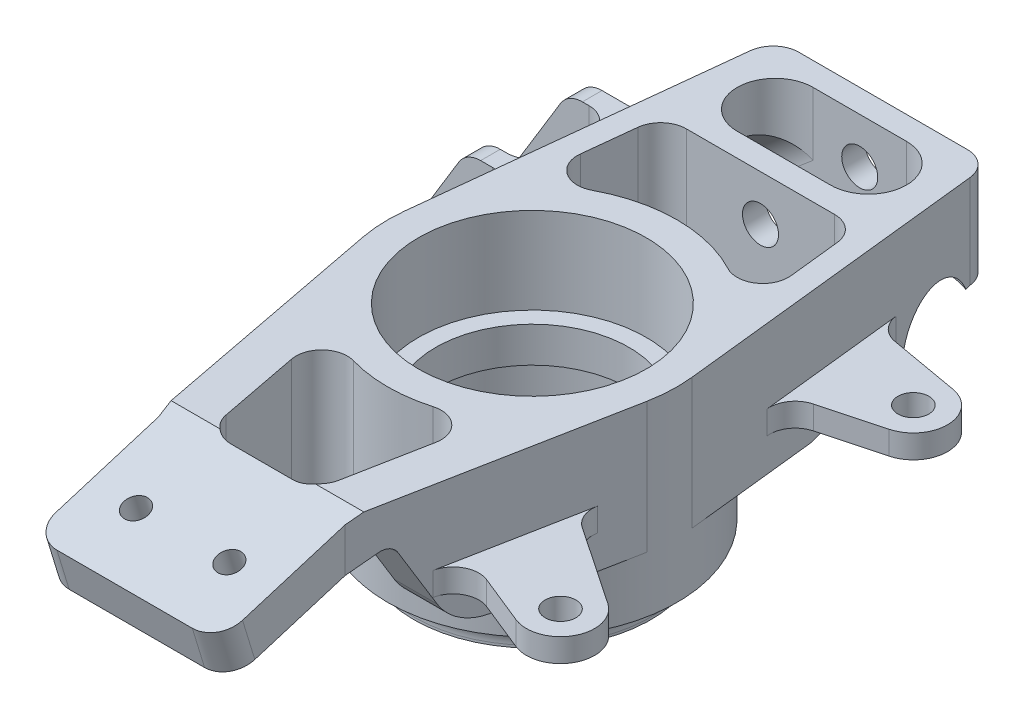
SolidWorks part; units mm, degrees
material "6061-T6 (SS)"
ref_plane "Front Plane" through (0, 0, 0) normal (0, 0, 1) x (1, 0, 0)
ref_plane "Top Plane" through (0, 0, 0) normal (0, 1, 0) x (1, 0, 0)
ref_plane "Right Plane" through (0, 0, 0) normal (1, 0, 0) x (0, 0, -1)
sketch "UBJ LBJ Geometry" plane through (0, 0, 0) normal (1, 0, 0) x (0, 0, -1)
  line L0 (0, 0) -> (0, -97.4059) construction
  line L1 (0, 0) -> (-30.7529, 0) construction
  line L2 (0, 22) -> (-45.5659, 22) construction
  line L3 (0, -10.5425) -> (-23.1063, -10.5425) construction
  line L4 (-84.7344, -51.66) -> (78.74, -22.958) construction
  line L5 (49.4563, 0) -> (49.4563, -88.2735) construction
  circle A0 centre (-84.7344, -51.66) radius 10.3251 construction
  circle A1 centre (78.74, -22.958) radius 10.3251 construction
  dimension "D7" = 20.6502
  dimension "D8" = 20.6502
  dimension "D1" = 22
  dimension "D2" = 32.5425
  dimension "D3" = 44.958
  dimension "D4" = 73.66
  dimension "D5" = 84.7344
  dimension "D6" = 78.74
  dimension "D9" = 29.2837
ref_plane "Wheel Face " through (0, 22, 0) normal (0, -1, 0) x (-1, 0, 0)
ref_plane "Upright Face" through (0, -10.5425, 0) normal (0, -1, 0) x (-1, 0, 0)
ref_plane "Tie Bracket Plane" through (0, 0, -49.4563) normal (0, 0, 1) x (1, 0, 0)
sketch "Tie Bracket Geometry" plane through (0, 0, -49.4563) normal (0, 0, 1) x (1, 0, 0)
  line L0 (0, -28.0995) -> (-60.5599, -51.7108) construction
  line L4 (0, 200000) -> (0, -200097.4059) construction
  circle A0 centre (-60.5599, -51.7108) radius 8.948 construction
  dimension "D1" = 65
  dimension "D2" = 68.7
sketch "Sketch1" plane through (0, 0, 0) normal (0, 0, 1) x (1, 0, 0)
  line L1 (-75.0953, -10.5425) -> (75.0953, -10.5425) construction
  line L2 (-39.37, -10.5425) -> (-39.37, -61.3425)
  line L3 (-39.37, -61.3425) -> (-32.258, -61.3425)
  line L4 (-32.258, -61.3425) -> (-32.258, -68.9625)
  line L5 (-32.258, -68.9625) -> (-30.9829, -68.9625)
  line L8 (-30.9829, -10.5425) -> (-30.9829, -34.0375)
  line L9 (-30.9829, -34.0375) -> (-26.289, -34.0375)
  line L10 (-26.289, -34.0375) -> (-26.289, -43.6895)
  line L11 (-26.289, -43.6895) -> (-30.9829, -43.6895)
  line L12 (-30.9829, -43.6895) -> (-30.9829, -68.9625)
  line L15 (-39.37, -10.5425) -> (-30.9829, -10.5425)
  line L17 (0, 0) -> (0, -23.5057) construction
  dimension "D1" = 9.652
  dimension "D2" = 61.9658
  dimension "D3" = 25.273
  dimension "D4" = 52.578
  dimension "D5" = 23.495
  dimension "D6" = 50.8
  dimension "D7" = 78.74
  dimension "D8" = 64.516
revolve "Bearing Housing Revolve" add sketch "Sketch1" angle 360 about L17
fillet "Bearing Housing Fillet" radius 6.985 1 edges at (0, -61.3425, 32.258)
sketch "Sketch2" plane through (0, -10.5425, 0) normal (0, -1, 0) x (-1, 0, 0)
  line L3 (39.37, -43.18) -> (39.37, 0)
  line L4 (-39.37, -43.18) -> (-39.37, 0)
  line L5 (39.37, -43.18) -> (-39.37, -43.18)
  circle A4 centre (0, 0) radius 39.37 construction
  arc A5 (39.37, 0) -> (-39.37, 0) centre (0, 0) cw
  dimension "D1" = 43.18
extrude "UBJ Prep" add sketch "Sketch2" along normal blind 35.56
sketch "Sketch3" plane through (-39.37, 0, 0) normal (-1, 0, 0) x (0, 0, 1)
  line L0 (-120.7672, 22) -> (120.7672, 22) construction
  line L1 (43.18, -10.5425) -> (72.0727, -10.5425)
  line L2 (72.0727, -10.5425) -> (110.937, -22.4245)
  line L3 (110.937, -22.4245) -> (107.5952, -33.355)
  line L4 (107.5952, -33.355) -> (68.7309, -21.473)
  line L6 (43.18, -46.1025) -> (43.18, -10.5425)
  line L7 (72.0727, -10.5425) -> (68.7309, -21.473) construction
  line L8 (104.3241, 12.415) -> (84.7344, -51.66) construction
  line L9 (55.3259, -39.0344) -> (64.3045, -23.2342)
  circle A0 centre (84.7344, -51.66) radius 12.7 construction
  arc A1 (43.18, -46.1025) -> (55.3259, -39.0344) centre (43.18, -32.1325) ccw
  arc A2 (68.7309, -21.473) -> (64.3045, -23.2342) centre (67.617, -25.1166) ccw
  dimension "D7" = 7.62
  dimension "D8" = 27.94
  dimension "D9" = 25.4
  dimension "D1" = 73.66
  dimension "D2" = 84.7344
  dimension "D3" = 11.43
  dimension "D4" = 40.64
  dimension "D5" = 17
  dimension "D6" = 16.51
extrude "UBJ Extrude " add sketch "Sketch3" against normal up to surface (78.74 mm away) up to face at (39.37, -28.3225, 21.59)
sketch "Sketch4" plane through (0, -0.4206, -0.1286) normal (0, -0.9563, -0.2924) x (1, 0, 0)
  line L0 (0, 112.6458) -> (0, 27.8969) construction
  line L1 (39.37, 112.6458) -> (-39.37, 112.6458) construction
  line L3 (-12.7, 96.1358) -> (12.7, 96.1358) construction
  circle A0 centre (-12.7, 96.1358) radius 3.2639
  circle A1 centre (12.7, 96.1358) radius 3.2639
  point P8 (0, 96.1358)
  dimension "D2" = 6.5278
  dimension "D1" = 25.4
extrude "Camber Block Holes" cut sketch "Sketch4" against normal up to surface (11.43 mm away) up to face at (0, -16.4835, 91.5049)
sketch "Sketch5" plane through (0, -46.1025, 0) normal (0, -1, 0) x (1, 0, 0)
  line L0 (-25.4, 107.5952) -> (-25.4, 76.3532)
  line L1 (25.4, 110.937) -> (39.37, 110.937)
  line L2 (39.37, 107.5952) -> (-39.37, 107.5952) construction
  line L4 (-25.4, 76.3532) -> (-38.6608, 7.4393)
  line L5 (25.4, 107.5952) -> (25.4, 76.3532)
  line L6 (25.4, 76.3532) -> (38.6608, 7.4393)
  line L7 (-25.4, 107.5952) -> (-25.4, 110.937)
  line L8 (39.37, 110.937) -> (-39.37, 110.937) construction
  line L9 (25.4, 107.5952) -> (25.4, 110.937)
  line L10 (-25.4, 110.937) -> (-39.37, 110.937)
  line L11 (-39.37, 110.937) -> (-39.37, 0)
  line L12 (39.37, 110.937) -> (39.37, 0)
  line L13 (-14.2785, 73.66) -> (14.2785, 73.66)
  line L14 (-14.2785, 73.66) -> (-22.1955, 32.517)
  line L15 (14.2785, 73.66) -> (22.1955, 32.517)
  arc A0 (-39.37, 0) -> (-38.6608, 7.4393) centre (0, 0) cw
  circle A1 centre (0, 0) radius 39.37 construction
  arc A2 (39.37, 0) -> (-39.37, 0) centre (0, 0) ccw construction
  arc A3 (39.37, 0) -> (38.6608, 7.4393) centre (0, 0) ccw
  arc A4 (-22.1955, 32.517) -> (22.1955, 32.517) centre (0, 0) cw
  point P31 (0, 73.66)
  dimension "D1" = 25.4
  dimension "D2" = 11.43
  dimension "D3" = 31.242
  dimension "D4" = 73.66
extrude "Weight Saving" cut sketch "Sketch5" against normal through all
fillet "Fillet2" radius 6.985 4 edges at (22.1955, -28.3225, 32.517) (-22.1955, -28.3225, 32.517) (14.2785, -17.0039, 73.66) (-14.2785, -17.0039, 73.66)
sketch "Sketch6" plane through (0, -10.5425, 0) normal (0, -1, 0) x (-1, 0, 0)
  line L0 (-39.37, 0) -> (-39.37, 40.64)
  line L1 (-39.37, 40.64) -> (39.37, 40.64)
  line L2 (39.37, 40.64) -> (39.37, 0)
  circle A0 centre (0, 0) radius 39.37 construction
  arc A1 (-39.37, 0) -> (39.37, 0) centre (0, 0) cw
  dimension "D1" = 40.64
extrude "LBJ Prep" add sketch "Sketch6" along normal blind 35.56
sketch "Sketch8" plane through (-39.37, 0, 0) normal (-1, 0, 0) x (0, 0, 1)
  line L0 (-40.64, -10.5425) -> (-95.4151, -10.5425)
  line L1 (-95.4151, -10.5425) -> (-95.4151, -35.9425)
  line L2 (-95.4151, -35.9425) -> (-89.0651, -35.9425)
  line L7 (-40.64, -46.1025) -> (-40.64, -10.5425)
  line L8 (-120.7672, 22) -> (120.7672, 22) construction
  line L9 (-89.0651, -35.9425) -> (-89.0651, -10.5425) construction
  line L10 (-89.0651, -35.9425) -> (-40.64, -46.1025)
  circle A0 centre (-78.74, -22.958) radius 10.3251 construction
  dimension "D3" = 20.6502
  dimension "D1" = 78.74
  dimension "D2" = 44.958
  dimension "D4" = 6.35
  dimension "D5" = 25.4
extrude "LBJ Area " add sketch "Sketch8" against normal up to surface (78.74 mm away) up to face at (39.37, -28.3225, -20.32)
sketch "Sketch7" plane through (0, -46.1025, 0) normal (0, -1, 0) x (1, 0, 0)
  line L0 (-12.7, -78.74) -> (12.7, -78.74) construction
  line L1 (0, -200000) -> (0, 200045.5659) construction
  line L2 (-12.7, -68.4149) -> (12.7, -68.4149)
  line L3 (-12.7, -89.0651) -> (12.7, -89.0651)
  line L4 (-29.21, -95.4151) -> (-39.1385, -4.2631)
  line L5 (39.37, -95.4151) -> (-39.37, -95.4151) construction
  line L6 (29.21, -95.4151) -> (39.1385, -4.2631)
  line L7 (-29.21, -95.4151) -> (-39.37, -95.4151)
  line L8 (-39.37, -95.4151) -> (-39.37, 0)
  line L9 (29.21, -95.4151) -> (39.37, -95.4151)
  line L10 (39.37, -95.4151) -> (39.37, 0)
  line L13 (-26.455, -62.0649) -> (26.455, -62.0649)
  line L14 (26.455, -62.0649) -> (30.5043, -24.8895)
  line L15 (-26.455, -62.0649) -> (-30.5043, -24.8895)
  arc A0 (-12.7, -68.4149) -> (-12.7, -89.0651) centre (-12.7, -78.74) ccw
  arc A1 (12.7, -89.0651) -> (12.7, -68.4149) centre (12.7, -78.74) ccw
  circle A2 centre (0, 0) radius 39.37 construction
  arc A3 (-39.37, 0) -> (39.37, 0) centre (0, 0) ccw construction
  arc A4 (39.37, 0) -> (39.1385, -4.2631) centre (0, 0) cw
  arc A5 (-39.37, 0) -> (-39.1385, -4.2631) centre (0, 0) ccw
  arc A6 (-30.5043, -24.8895) -> (30.5043, -24.8895) centre (0, 0) ccw
  point P4 (0, -78.74)
  point P28 (0, -62.0649)
  dimension "D1" = 78.74
  dimension "D2" = 20.6502
  dimension "D3" = 25.4
  dimension "D4" = 10.16
  dimension "D5" = 6.35
  dimension "D6" = 6.35
extrude "LBJ Taper And Slot" cut sketch "Sketch7" against normal up to surface (35.56 mm away) up to face at (0, -10.5425, 30.9829)
fillet "Fillet3" radius 6.985 4 edges at (26.455, -26.0749, -62.0649) (-26.455, -26.0749, -62.0649) (30.5043, -28.3225, -24.8895) (-30.5043, -28.3225, -24.8895)
extrude "LBJ Holes 3/8 Close Fit Hole" cut sketch "Sketch9" against normal up to surface (33.3502 mm away) up to face at (0, -26.0749, -62.0649)
sketch "Sketch9" plane through (0, 0, -95.4151) normal (0, 0, -1) x (-1, 0, 0)
  circle A0 centre (0, -22.958) radius 4.9022
  dimension "D2" = 9.8044
  dimension "D1" = 22.958
ref_plane "Brake Mounting Plane" through (0, -30.7025, 0) normal (0, 1, 0) x (1, 0, 0)
sketch "Sketch10" plane through (0, -30.7025, 0) normal (0, 1, 0) x (1, 0, 0)
  line L0 (87.9814, 0) -> (161.3053, 0) construction
  line L1 (0, 72.9505) -> (0, 47.1638) construction
  line L2 (55.6514, 48) -> (55.6514, -48) construction
  line L3 (58.0532, 39.0362) -> (35.9947, 33.1256)
  line L4 (39.1385, 4.2631) -> (29.21, 95.4151) construction
  line L5 (35.9947, 33.1256) -> (32.9114, 61.4328)
  line L6 (32.9114, 61.4328) -> (57.2629, 57.139)
  line L7 (60.8407, -40.3065) -> (35.6109, -23.2888)
  line L8 (26.2237, -72.0727) -> (38.6608, -7.4393) construction
  line L9 (35.6109, -23.2888) -> (30.8575, -47.9914)
  line L10 (30.8575, -47.9914) -> (52.1751, -56.6043)
  circle A0 centre (55.6514, 48) radius 4.2
  circle A1 centre (55.6514, -48) radius 4.2
  arc A2 (52.1751, -56.6043) -> (60.8407, -40.3065) centre (55.6514, -48) ccw
  arc A3 (58.0532, 39.0362) -> (57.2629, 57.139) centre (55.6514, 48) ccw
  point P7 (55.6514, 0)
  dimension "D2" = 8.4
  dimension "D3" = 5.08
  dimension "D4" = 5.08
  dimension "D1" = 96
  dimension "D5" = 55.6514
  dimension "D6" = 80
  dimension "D7" = 75
  dimension "D8" = 56
  dimension "D9" = 68
extrude "Brake Mounts" add sketch "Sketch10" against normal blind 6.35
fillet "Fillet4" radius 6.985 4 edges at (35.6109, -33.8775, 23.2888) (30.8575, -33.8775, 47.9914) (35.9947, -33.8775, -33.1256) (32.9114, -33.8775, -61.4328)
sketch "Sketch17" plane through (0, -37.0525, 0) normal (0, -1, 0) x (1, 0, 0)
  line L1 (36.4827, 18.7581) -> (29.2533, 56.3282) construction
  line L3 (32.3437, -66.6449) -> (36.6432, -27.1723) construction
  line L6 (57.2629, -57.139) -> (38.0747, -60.5224) construction
  line L12 (60.8407, 40.3065) -> (39.4359, 25.8688) construction
  circle A0 centre (39.9101, 39.5927) radius 4.7625
  circle A1 centre (41.7973, -47.2925) radius 4.7625
  dimension "D1" = 9.525
  dimension "D2" = 9.525
  dimension "D3" = 2.54
  dimension "D4" = 2.54
  dimension "D5" = 7.62
  dimension "D6" = 6.35
extrude "rotor Cut " [suppressed] cut sketch "Sketch17" against normal up to surface (6.35 mm away) up to plane "Brake Mounting Plane"
sketch "Sketch16" plane through (0, -46.1025, 0) normal (0, 1, 0) x (1, 0, 0)
  line L0 (-38.6345, 8.89) -> (-55.7371, 8.89)
  line L1 (-38.6608, -7.4393) -> (-26.2237, -72.0727) construction
  line L2 (-55.7371, 8.89) -> (-55.7371, -8.89)
  line L3 (-55.7371, -8.89) -> (-38.3816, -8.89)
  line L5 (-29.21, 95.4151) -> (-39.1385, 4.2631) construction
  line L6 (-38.6345, 8.89) -> (-38.3816, -8.89)
  circle A0 centre (-46.609, 0) radius 5.9531
  point P8 (-55.7371, 0)
  dimension "D1" = 3.175
  dimension "D3" = 11.9062
  dimension "D2" = 46.609
  dimension "D4" = 17.78
extrude "Speed Sensor Mount" add sketch "Sketch16" along normal blind 5.08
fillet "Speed Sensor Fillet" radius 6.985 4 edges at (-55.7371, -43.5625, 8.89) (-55.7371, -43.5625, -8.89) (-38.3816, -43.5625, 8.89) (-38.6345, -43.5625, -8.89)
thread "15/32-32" pitch 0.9071 method cut profile "Thread Profile1" start angle 0, offset 1, length 10, pitch 0.7937, diameter 11.9062
ref_plane "Plane1" through (-40.6559, -45.1025, 0) normal (0, 0, 1) x (1, 0, 0)
sketch "Thread Profile1" plane through (-40.6559, -45.1025, 0) normal (0, 0, 1) x (1, 0, 0)
  line L0 (0, 0) -> (0, 0.9071) construction
  line L1 (0, 0) -> (0.491, 0.2835)
  line L2 (0.491, 0.2835) -> (0.491, 0.3969)
  line L3 (0.491, 0.3969) -> (0, 0.6804)
  line L4 (0.491, 0.3402) -> (0, 0.3402) construction
  line L11 (0, 0) -> (0, 0.6804)
  point P2 (0, 0)
  dimension "Pitch" = 0.9071
  dimension "Profile_Angle" = 60
  dimension "Profile_Land" = 0.1134
  dimension "Profile_Height" = 0.491
sketch "Sketch12" plane through (0, 0, -49.4563) normal (0, 0, 1) x (1, 0, 0)
  line L0 (0, 3.2946) -> (0, -38.5659) construction
  line L1 (-90.5661, 0) -> (-38.2005, 0) construction
  line L2 (-68.726, -10.5425) -> (-68.726, -51.7108)
  line L3 (-52.3938, -10.5425) -> (-52.3938, -51.7108)
  line L4 (-68.726, -10.5425) -> (-52.3938, -10.5425)
  line L6 (-75.0953, -10.5425) -> (75.0953, -10.5425) construction
  circle A0 centre (-60.5599, -51.7108) radius 3.2639
  arc A1 (-68.726, -51.7108) -> (-52.3938, -51.7108) centre (-60.5599, -51.7108) ccw
  dimension "D1" = 6.5278
  dimension "D2" = 4.9022
extrude "Initial Toe Bracket" add sketch "Sketch12" along normal blind 16.51 and the other way blind 16.51 separate body
sketch "Sketch13" plane through (-52.3938, 0, 0) normal (1, 0, 0) x (0, 0, -1)
  line L0 (32.9463, -16.8925) -> (65.9663, -16.8925)
  line L1 (65.9663, -51.7108) -> (65.9663, -10.5425) construction
  line L2 (65.9663, -16.8925) -> (65.9663, -38.4825)
  line L3 (32.9463, -16.8925) -> (32.9463, -38.4825)
  line L4 (200000, -10.5425) -> (-200023.1063, -10.5425) construction
  line L5 (32.9463, -38.4825) -> (65.9663, -38.4825)
  line L6 (32.9463, -51.7108) -> (32.9463, -10.5425) construction
  dimension "D1" = 6.35
  dimension "D2" = 21.59
extrude "Toe Bracket Connection to Upright" add sketch "Sketch13" along normal up to surface (19.9762 mm away) up to face at (-34.7109, -33.4025, -44.9123)
sketch "Sketch14" plane through (0, 0, -65.9663) normal (0, 0, -1) x (-1, 0, 0)
  line L0 (52.3938, -16.8925) -> (68.726, -16.8925)
  line L1 (68.726, -10.5425) -> (68.726, -51.7108) construction
  line L2 (68.726, -16.8925) -> (68.726, -10.5425)
  line L3 (68.726, -10.5425) -> (52.3938, -10.5425)
  line L4 (52.3938, -10.5425) -> (52.3938, -16.8925)
extrude "Excess Toe Bracket Cut" cut sketch "Sketch14" against normal up to surface (33.02 mm away) up to face at (-52.382, -30.4278, -32.9463)
sketch "Sketch19" plane through (0, 0, -32.9463) normal (0, 0, 1) x (1, 0, 0)
  line L1 (-43.6343, -38.4825) -> (-52.3938, -38.4825)
  line L2 (-52.3938, -38.4825) -> (-53.0672, -54.958)
  line L3 (-36.0143, -38.4825) -> (-52.3938, -38.4825) construction
  line L4 (-36.0143, -16.8925) -> (-36.0143, -38.4825) construction
  line L5 (-53.0672, -54.958) -> (-46.8388, -40.5862)
  arc A0 (-68.726, -51.7108) -> (-52.3938, -51.7108) centre (-60.5599, -51.7108) ccw construction
  arc A1 (-43.6343, -38.4825) -> (-46.8388, -40.5862) centre (-43.6343, -41.975) ccw
  dimension "D2" = 6.985
  dimension "D1" = 7.62
extrude "Adding To Toe" add sketch "Sketch19" against normal up to surface (33.02 mm away) up to face at (-51.1792, -37.0563, -65.9663)
sketch "Sketch20" plane through (0, 0, -32.9463) normal (0, 0, 1) x (1, 0, 0)
  line L0 (-50.946, -16.8925) -> (-68.726, -16.8925)
  line L1 (-36.0143, -16.8925) -> (-68.726, -16.8925) construction
  line L2 (-68.726, -16.8925) -> (-68.726, -46.1025)
  line L3 (-68.726, -16.8925) -> (-68.726, -51.7108) construction
  line L4 (-68.726, -46.1025) -> (-50.946, -16.8925)
  dimension "D1" = 17.78
  dimension "D2" = 29.21
extrude "Cut-Extrude1" cut sketch "Sketch20" against normal up to surface (33.02 mm away) up to face at (-49.6376, -37.6998, -65.9663)
sketch "Sketch15" plane through (-68.726, 0, 0) normal (-1, 0, 0) x (0, 0, 1)
  line L0 (-60.6323, -16.8925) -> (-38.2803, -16.8925)
  line L1 (-38.2803, -16.8925) -> (-38.2803, -59.8769)
  line L2 (-65.9663, -59.8769) -> (-32.9463, -59.8769) construction
  line L3 (-38.2803, -59.8769) -> (-60.6323, -59.8769)
  line L4 (-60.6323, -59.8769) -> (-60.6323, -16.8925)
  line L6 (-49.4563, -25.7825) -> (-49.4563, -39.109) construction
  line L8 (-32.9463, -16.8925) -> (-65.9663, -16.8925) construction
  point P9 (-49.4563, -16.8925)
  point P11 (-49.4563, -16.8925)
  dimension "D1" = 22.352
extrude "Toe Bracket Slot" cut sketch "Sketch15" against normal blind 30.48
fillet "Toe Bracket Fillet" radius 6.985 2 edges at (-32.4176, -27.6875, -65.9663) (-36.0143, -27.6875, -32.9463)
fillet "Fillet7" radius 6.985 4 edges at (-68.726, -46.1025, -35.6133) (-68.726, -46.1025, -63.2993) (-50.946, -16.8925, -63.2993) (-50.946, -16.8925, -35.6133)
fillet "Inside Toe Fillet" radius 6.985 2 edges at (-38.246, -27.6875, -38.2803) (-38.246, -27.6875, -60.6323)
fillet "Outside Fillets" radius 6.985 4 edges at (-25.4, -27.8897, 109.2661) (25.4, -27.8897, 109.2661) (29.21, -23.2425, -95.4151) (-29.21, -23.2425, -95.4151)
sketch "Angle Reference" plane through (0, 0, -95.4151) normal (0, 0, -1) x (-1, 0, 0)
  line L0 (0, -22.958) -> (32.5253, -73.0426) construction
  line L1 (0, 0) -> (0, -88.2735) construction
  line L2 (0, -22.958) -> (69.6053, -82.0294) construction
  dimension "D1" = 33
  dimension "D2" = 16.68
ref_plane "Plane2" through (0, -22.958, -78.74) normal (-0.7624, -0.6471, 0) x (0, 0, 1)
sketch "Sketch22" plane through (0, -22.958, -78.74) normal (-0.7624, -0.6471, 0) x (0, 0, 1)
  line L0 (0, 4.572) -> (0, -5.588) construction
  line L3 (10.3251, 4.572) -> (10.3251, -5.588)
  line L4 (-10.3251, 4.572) -> (-10.3251, -5.588)
  arc A2 (10.3251, 4.572) -> (-10.3251, 4.572) centre (0, 4.572) ccw
  arc A3 (-10.3251, -5.588) -> (10.3251, -5.588) centre (0, -5.588) ccw
  point P2 (0, -0.508)
  dimension "D1" = 20.6502
  dimension "D2" = 4.572
  dimension "D3" = 10.16
extrude "Angle Slot Cut" cut sketch "Sketch22" along normal through all
mirror "Mirror1" about plane through (0, 0, 0) normal (1, 0, 0) of "Angle Slot Cut"
equation "\"Wheel_Offset\"= 22mm"
equation "\"HUB_to_UBJ_Lat\"= 2.9in"
equation "\"Hub_to_UBJ_Vert\"= 3.336in"
equation "\"Hub_to_LBJ_Lat\"= 1.77in"
equation "\"Hub_to_LBJ_Vert\"= 3.1in"
equation "\"Wheel_face_to_Upright_back\"= 1.2812in'This is the distance between the whee face to the upright back."
equation "\"UBJ_Angle\"= 17deg"
equation "\"D2@UBJ LBJ Geometry\" = \"Wheel_face_to_Upright_back\""
equation "\"D3@UBJ LBJ Geometry\" = \"Hub_to_LBJ_Lat\""
equation "\"D4@UBJ LBJ Geometry\" = \"HUB_to_UBJ_Lat\""
equation "\"D5@UBJ LBJ Geometry\" = \"Hub_to_UBJ_Vert\""
equation "\"D6@UBJ LBJ Geometry\" = \"Hub_to_LBJ_Vert\""
equation "\"D1@Sketch3\"=\"HUB_to_UBJ_Lat\""
equation "\"D2@Sketch3\"=\"Hub_to_UBJ_Vert\""
equation "\"D1@Sketch8\"=\"Hub_to_LBJ_Vert\""
equation "\"D2@Sketch8\"=\"Hub_to_LBJ_Lat\""
equation "\"Hub_Tie_Bracket_Vert\"= 2in'(Not Given) Ask Sus and Controls later"
equation "\"Tie_Beta\"= 21.3deg'From FE11 Master "
equation "\"Toe_Arm\"= 65mm'From FE11 Master (Assume Dist start at KPI)"
equation "\"D1@Sketch7\"=\"Hub_to_LBJ_Vert\""
equation "\"D1@Sketch9\"=\"Hub_to_LBJ_Lat\"-\"Wheel_Offset\""
equation "\"D1@Tie Bracket Geometry\" = \"Toe_Arm\""
equation "\"D2@Tie Bracket Geometry\" = 90 - \"Tie_Beta\""
equation "\"oranizeBlock\"= 0"
equation "\"BrakeAngle\"= 65deg"
equation "\"D5@Sketch3\"=\"UBJ_Angle\""
equation "\"D1@Sketch7\"=\"Hub_to_LBJ_Lat\""
